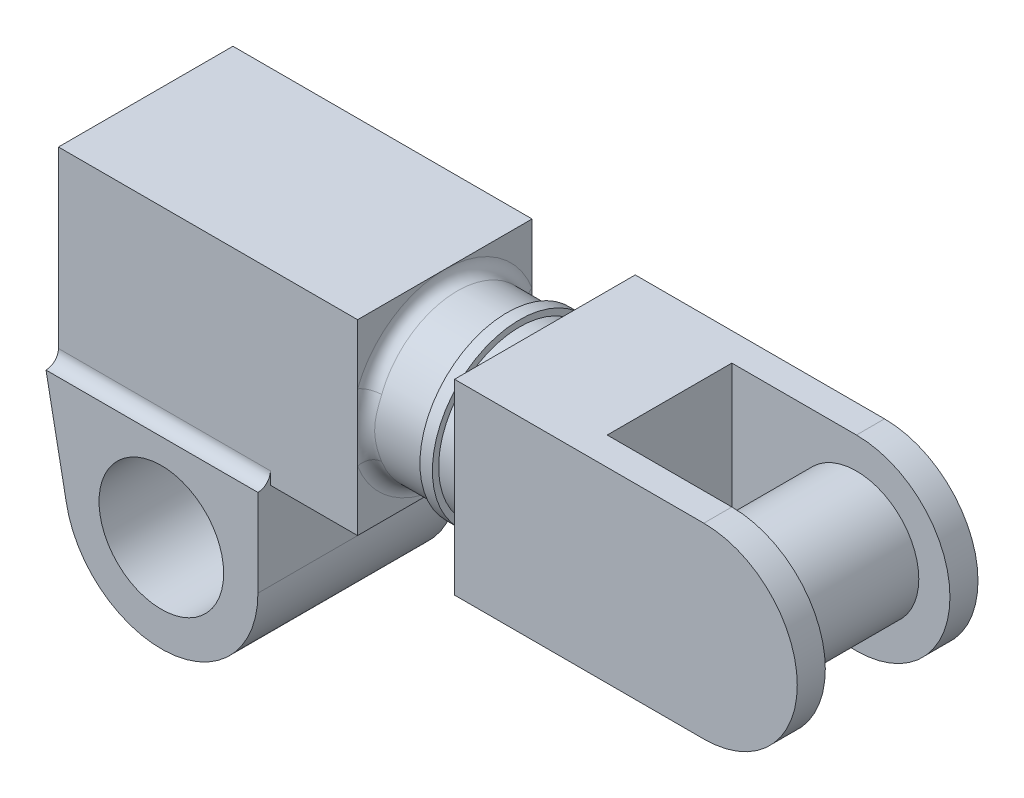
SolidWorks part; units mm, degrees
ref_plane "Front Plane" through (0, 0, 0) normal (0, 0, 1) x (1, 0, 0)
ref_plane "Top Plane" through (0, 0, 0) normal (0, 1, 0) x (1, 0, 0)
ref_plane "Right Plane" through (0, 0, 0) normal (1, 0, 0) x (0, 0, -1)
sketch "Sketch2" plane through (0, 0, 0) normal (1, 0, 0) x (0, 0, -1)
  line L1 (70, 75) -> (-70, 75)
  line L2 (70, 75) -> (70, -75)
  line L3 (70, -75) -> (-70, -75)
  line L4 (-70, 75) -> (-70, -75)
  line L5 (70, 75) -> (-70, -75) construction
  line L6 (70, -75) -> (-70, 75) construction
  point P0 (0, 0)
  dimension "D1" = 140
  dimension "D2" = 150
extrude "Boss-Extrude1" add sketch "Sketch2" along normal blind 240
sketch "Sketch3" plane through (240, 0, 0) normal (1, 0, 0) x (0, 0, -1)
  circle A0 centre (0, 0) radius 65
extrude "Boss-Extrude2" add sketch "Sketch3" along normal blind 50
sketch "Sketch4" plane through (290, 0, 0) normal (1, 0, 0) x (0, 0, -1)
  circle A0 centre (0, 0) radius 70
extrude "Boss-Extrude3" add sketch "Sketch4" along normal blind 10
sketch "Sketch6" plane through (0, 0, 0) normal (0, 0, 1) x (1, 0, 0)
  line L0 (0, -75) -> (16.2188, -158.4383)
  line L1 (0, 75) -> (0, -75) construction
  line L2 (170.0448, -145) -> (170.0448, -75)
  line L3 (240, -75) -> (0, -75) construction
  line L4 (170.0448, -75) -> (0, -75)
  circle A0 centre (92.5448, -145) radius 50
  arc A1 (16.2188, -158.4383) -> (170.0448, -145) centre (92.5448, -145) ccw
  dimension "D1" = 100
  dimension "D2" = 155
  dimension "D3" = 191
  dimension "D4" = 85
  dimension "D5" = 70
extrude "Boss-Extrude4" add sketch "Sketch6" along normal mid plane 160
fillet "Fillet1" radius 10 3 edges at (240, 0, -65) (85.0224, -75, -70) (85.0224, -75, 70)
sketch "Sketch7" plane through (300, 0, 0) normal (1, 0, 0) x (0, 0, -1)
  circle A0 centre (0, 0) radius 65
extrude "Boss-Extrude5" add sketch "Sketch7" along normal blind 20
sketch "Sketch8" plane through (0, 0, 0) normal (0, 0, 1) x (1, 0, 0)
  line L0 (520.2785, -75) -> (320.2785, -75)
  line L1 (320.2785, -75) -> (320.2785, 75)
  line L2 (320.2785, 75) -> (520.2785, 75)
  arc A0 (520.2785, -75) -> (520.2785, 75) centre (520.2785, 0) ccw
  dimension "D1" = 150
  dimension "D2" = 200
extrude "Boss-Extrude6" add sketch "Sketch8" along normal mid plane 145 separate body
sketch "Sketch9" plane through (0, 0, 0) normal (0, 0, 1) x (1, 0, 0)
  line L0 (520.2785, 75) -> (420.2785, 75)
  line L1 (520.2785, 75) -> (320.2785, 75) construction
  line L2 (420.2785, 75) -> (420.2785, -75)
  line L3 (320.2785, -75) -> (520.2785, -75) construction
  line L4 (420.2785, -75) -> (520.2785, -75)
  arc A0 (520.2785, -75) -> (520.2785, 75) centre (520.2785, 0) ccw construction
  arc A1 (520.2785, -75) -> (520.2785, 75) centre (520.2785, 0) ccw
extrude "Cut-Extrude1" cut sketch "Sketch9" against normal mid plane 100
sketch "Sketch10" plane through (0, 0, -50) normal (0, 0, 1) x (1, 0, 0)
  circle A0 centre (520.2785, 0) radius 50
extrude "Boss-Extrude7" add sketch "Sketch10" along normal blind 100
